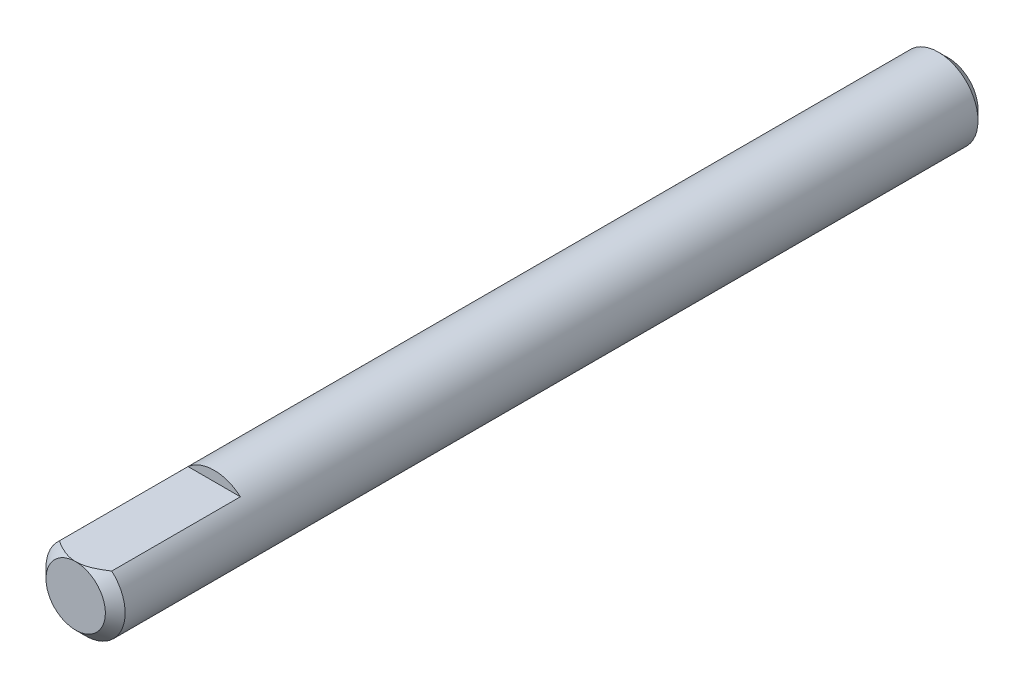
SolidWorks part; units mm, degrees
material "Литая легированная сталь"
ref_plane "Спереди" through (0, 0, 0) normal (0, 0, 1) x (1, 0, 0)
ref_plane "Сверху" through (0, 0, 0) normal (0, 1, 0) x (1, 0, 0)
ref_plane "Справа" through (0, 0, 0) normal (1, 0, 0) x (0, 0, -1)
sketch "Эскиз2" plane through (0, 0, 0) normal (0, 0, 1) x (1, 0, 0)
  circle A0 centre (0, 0) radius 2
  dimension "D1" = 4
extrude "Бобышка-Вытянуть1" add sketch "Эскиз2" along normal blind 44.1
sketch "Эскиз3" plane through (0, 0, 44.1) normal (0, 0, 1) x (1, 0, 0)
  line L0 (0, -2) -> (0, 1.5) construction
  line L1 (1.3229, 1.5) -> (-1.3229, 1.5)
  circle A0 centre (0, 0) radius 2 construction
  arc A1 (1.3229, 1.5) -> (-1.3229, 1.5) centre (0, 0) ccw
  dimension "D1" = 3.5
extrude "Вырез-Вытянуть1" cut sketch "Эскиз3" against normal blind 7
chamfer "Фаска1" distance 0.5 angle 45 1 edges at (2, 0, 0)
chamfer "Фаска2" distance 0.5 angle 45 1 edges at (0, -2, 44.1)
